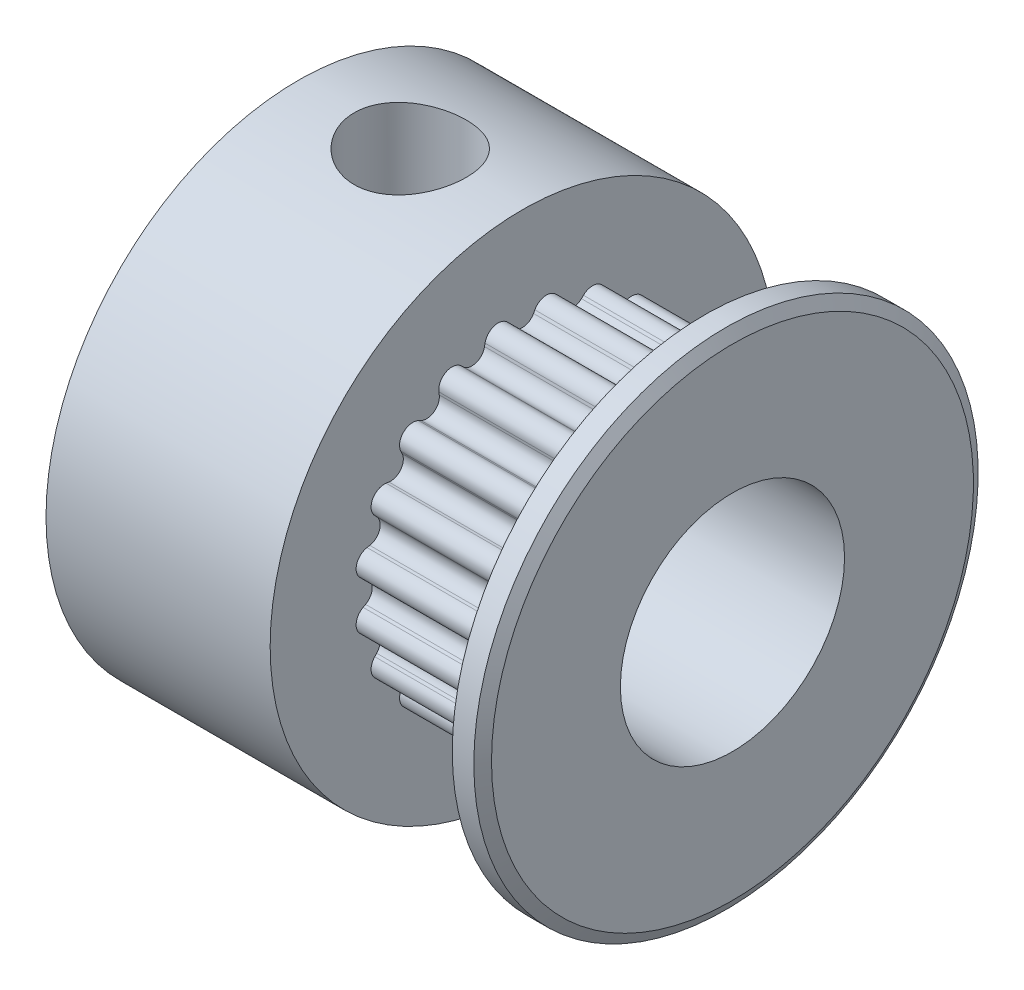
SolidWorks part; units mm, degrees
ref_plane "Front Plane" through (0, 0, 0) normal (0, 0, 1) x (1, 0, 0)
ref_plane "Top Plane" through (0, 0, 0) normal (0, 1, 0) x (1, 0, 0)
ref_plane "Right Plane" through (0, 0, 0) normal (1, 0, 0) x (0, 0, -1)
sketch "Sketch1" plane through (0, 0, 0) normal (0, 0, 1) x (1, 0, 0)
  line L0 (0, 0) -> (8.5, 0) construction
  line L1 (0, 0) -> (0, 9)
  line L2 (0, 9) -> (1, 9)
  line L3 (1, 9) -> (1, 6)
  line L4 (1, 6) -> (7.5, 6)
  line L5 (7.5, 6) -> (7.5, 9)
  line L6 (7.5, 9) -> (8.5, 9)
  line L7 (8.5, 9) -> (8.5, 0)
  line L8 (0, 0) -> (8.5, 0)
  dimension "D1" = 8.5
  dimension "D2" = 18
  dimension "D3" = 12
  dimension "D4" = 6.5
revolve "Revolve1" add sketch "Sketch1" angle 360 about L0
chamfer "Chamfer1" distance 0.4 angle 30 1 edges at (8.5, 0, 9) first distance on face at (8.5, 0, 9)
sketch "Sketch2" plane through (8.5, 0, 0) normal (1, 0, 0) x (0, 0, -1)
  circle A0 centre (0, 0) radius 2.5
  dimension "D1" = 5
extrude "Cut-Extrude1" cut sketch "Sketch2" against normal through all
sketch "Sketch3" plane through (8.5, 0, 0) normal (1, 0, 0) x (0, 0, -1)
  circle A0 centre (0, 0) radius 3.25
  circle A1 centre (0, 0) radius 4
  dimension "D1" = 8
  dimension "D2" = 6.5
extrude "Cut-Extrude2" cut sketch "Sketch3" against normal blind 0.5
sketch "Sketch4" plane through (0, 0, 0) normal (-1, 0, 0) x (0, 0, 1)
  circle A0 centre (0, 0) radius 3.25
  circle A1 centre (0, 0) radius 4
  dimension "D1" = 8
  dimension "D2" = 6.5
extrude "Cut-Extrude3" cut sketch "Sketch4" against normal blind 0.5
sketch "Sketch5" plane through (8.5, 0, 0) normal (1, 0, 0) x (0, 0, -1)
  line L0 (0, 0) -> (0, 3.3722) construction
  line L1 (0, 0) -> (-1.3453, 8.4941) construction
  line L2 (0, 0) -> (1.3453, 8.4941) construction
  line L3 (-0.3995, 5.5946) -> (-0.4473, 5.6832)
  line L4 (0, 0) -> (0, 8.6) construction
  line L5 (0, 5.3564) -> (0, 5.8104) construction
  line L6 (-0.4473, 5.6832) -> (0, 0) construction
  line L7 (0, 5.8104) -> (0, 6) construction
  line L8 (0, 8.6278) -> (0, 3.3722) construction
  line L9 (0.4473, 5.6832) -> (0.3995, 5.5946)
  circle A0 centre (0, 0) radius 6 construction
  arc A1 (-0.3995, 5.5946) -> (0.3995, 5.5946) centre (0, 5.8104) ccw
  arc A2 (-0.4473, 5.6832) -> (-0.9386, 5.9261) centre (-0.8644, 5.4578) ccw
  arc A3 (0.9386, 5.9261) -> (0.4473, 5.6832) centre (0.8644, 5.4578) ccw
  arc A4 (0.9386, 5.9261) -> (-0.9386, 5.9261) centre (0, 0) ccw
  circle A5 centre (0, 0) radius 8.6 construction
  dimension "D1" = 6
  dimension "D5" = 18
  dimension "D6" = 9
  dimension "D3" = 5.8104
  dimension "D4" = 0.4741
  dimension "D2" = 4.5
extrude "Cut-Extrude4" cut sketch "Sketch5" against normal blind 6.5 from offset 1 offset against normal yes
ref_axis "Axis1" through (0, 0, 0) along (1, 0, 0)
pattern_circular "CirPattern1" count 20 every 18 about axis through (0, 0, 0) along (1, 0, 0) of "Cut-Extrude4"
sketch "Sketch6" plane through (0, 0, 0) normal (-1, 0, 0) x (0, 0, 1)
  circle A0 centre (0, 0) radius 9
  circle A1 centre (0, 0) radius 9
  circle A2 centre (0, 0) radius 9
  circle A3 centre (0, 0) radius 4
  circle M2 centre (0, 0) radius 4
  circle M3 centre (0, 0) radius 9
  dimension "D2" = 18
  dimension "D1" = 0
extrude "Boss-Extrude1" add sketch "Sketch6" along normal blind 7 contours M3 M2 region at (0, 0, -8.7454)
sketch "Sketch7" plane through (-7, 0, 0) normal (-1, 0, 0) x (0, 0, 1)
  circle A0 centre (0, 0) radius 4
extrude "Cut-Extrude6" cut sketch "Sketch7" against normal blind 16
sketch "Sketch8" plane through (0, 0, 0) normal (0, 0, 1) x (1, 0, 0)
  line L0 (-7, 9) -> (-7, -9) construction
  line L1 (0, 0) -> (8.5, 0) construction
  circle A0 centre (-3, 0) radius 2
  dimension "D2" = 4
  dimension "D1" = 4
extrude "Cut-Extrude7" cut sketch "Sketch8" against normal blind 16
pattern_circular "CirPattern2" count 2 every 90 about axis through (0, 0, 0) along (1, 0, 0) of "Cut-Extrude7"
sketch "Sketch9" plane through (7.5, 0, 0) normal (-1, 0, 0) x (0, 0, 1)
  circle A0 centre (0, 0) radius 6 construction
  dimension "D1" = 12
